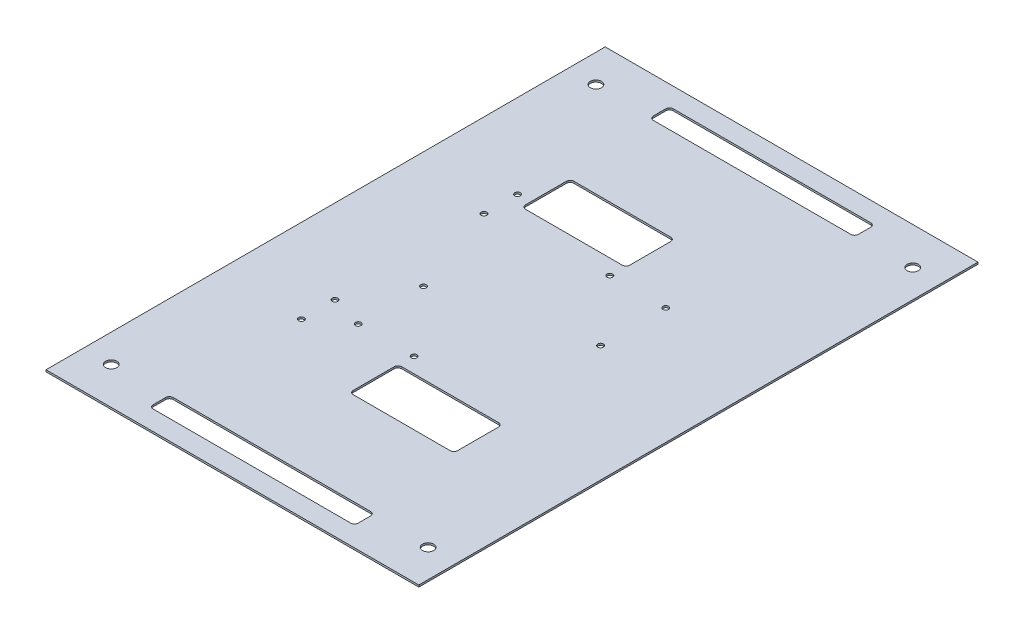
SolidWorks part; units mm, degrees
ref_plane "Plan de face" through (0, 0, 0) normal (0, 0, 1) x (1, 0, 0)
ref_plane "Plan de dessus" through (0, 0, 0) normal (0, 1, 0) x (1, 0, 0)
ref_plane "Plan de droite" through (0, 0, 0) normal (1, 0, 0) x (0, 0, -1)
sketch "Esquisse1" plane through (0, 0, 0) normal (0, 1, 0) x (1, 0, 0)
  line L0 (-2, -76.175) -> (42, -76.175) construction
  line L1 (-100, -150) -> (100, -150)
  line L2 (-100, -150) -> (-100, 150)
  line L3 (-100, 150) -> (100, 150)
  line L4 (100, -150) -> (100, 150)
  line L5 (-100, -150) -> (100, 150) construction
  line L6 (-100, 150) -> (100, -150) construction
  line L7 (-6, -53.175) -> (46, -53.175)
  line L8 (-8, -55.175) -> (-8, -77.175)
  line L9 (-6, -79.175) -> (46, -79.175)
  line L10 (48, -55.175) -> (48, -77.175)
  line L11 (47, -56.175) -> (-7, -56.175) construction
  line L12 (0, 0) -> (0, -150) construction
  line L13 (47, -150) -> (47, -53.175) construction
  line L14 (100, 0) -> (-100, 0) construction
  line L15 (-7, -53.175) -> (-7, -150) construction
  line L16 (0, 150) -> (0, 0) construction
  line L17 (7, 76.175) -> (-47, 76.175) construction
  line L18 (-46, 79.175) -> (6, 79.175)
  line L19 (-48, 77.175) -> (-48, 55.175)
  line L20 (-46, 53.175) -> (6, 53.175)
  line L21 (8, 77.175) -> (8, 55.175)
  line L22 (-47, 56.175) -> (7, 56.175) construction
  line L23 (-47, 56.175) -> (-47, 150) construction
  line L24 (-55, 0) -> (-55, 75.3308) construction
  line L25 (7, 56.175) -> (7, 150) construction
  line L26 (-53, -139.5001) -> (53, -139.5001)
  line L27 (55, -137.5001) -> (55, -130.7728)
  line L28 (53, -128.7728) -> (-53, -128.7728)
  line L29 (-60, -138.5001) -> (60, -138.5001) construction
  line L30 (57.5, -129.5001) -> (-57.5, -129.5001) construction
  line L31 (-55, -137.5001) -> (-55, -130.7728)
  line L32 (-55, 137.5001) -> (-55, 130.7728)
  line L33 (53, 128.7728) -> (-53, 128.7728)
  line L34 (55, 137.5001) -> (55, 130.7728)
  line L35 (-53, 139.5001) -> (53, 139.5001)
  arc A0 (46, -79.175) -> (48, -77.175) centre (46, -77.175) ccw
  arc A1 (48, -55.175) -> (46, -53.175) centre (46, -55.175) ccw
  arc A2 (-6, -53.175) -> (-8, -55.175) centre (-6, -55.175) ccw
  arc A3 (-8, -77.175) -> (-6, -79.175) centre (-6, -77.175) ccw
  arc A4 (8, 55.175) -> (6, 53.175) centre (6, 55.175) cw
  arc A5 (8, 77.175) -> (6, 79.175) centre (6, 77.175) ccw
  arc A6 (-46, 79.175) -> (-48, 77.175) centre (-46, 77.175) ccw
  arc A7 (-48, 55.175) -> (-46, 53.175) centre (-46, 55.175) ccw
  circle A8 centre (-37.5, -45) radius 1.5
  circle A9 centre (-7.5, -45) radius 1.5
  circle A10 centre (-37.5, -10) radius 1.5
  circle A11 centre (37.5, 10) radius 1.5
  circle A12 centre (37.5, 45) radius 1.5
  circle A13 centre (7.5, 45) radius 1.5
  circle A14 centre (85, 130) radius 3
  circle A15 centre (-85, 130) radius 3
  circle A16 centre (85, -130) radius 3
  circle A17 centre (-85, -130) radius 3
  circle A18 centre (-55, 40) radius 1.5
  circle A19 centre (-55, 58) radius 1.5
  circle A20 centre (-55, -58) radius 1.5
  circle A21 centre (-55, -40) radius 1.5
  arc A22 (53, -128.7728) -> (55, -130.7728) centre (53, -130.7728) cw
  arc A23 (53, -139.5001) -> (55, -137.5001) centre (53, -137.5001) ccw
  arc A24 (-55, -137.5001) -> (-53, -139.5001) centre (-53, -137.5001) ccw
  arc A25 (-55, -130.7728) -> (-53, -128.7728) centre (-53, -130.7728) cw
  arc A26 (-55, 130.7728) -> (-53, 128.7728) centre (-53, 130.7728) ccw
  arc A27 (-55, 137.5001) -> (-53, 139.5001) centre (-53, 137.5001) cw
  arc A28 (53, 128.7728) -> (55, 130.7728) centre (53, 130.7728) ccw
  arc A29 (53, 139.5001) -> (55, 137.5001) centre (53, 137.5001) cw
  point P0 (0, 0)
  point P93 (0, -139.5001)
  point P101 (0, -128.7728)
  point P107 (55, -128.7728)
  point P110 (55, -139.5001)
  point P113 (-55, -139.5001)
  point P116 (-55, -128.7728)
  point P119 (-55, 128.7728)
  point P122 (-55, 139.5001)
  point P125 (55, 128.7728)
  point P128 (55, 139.5001)
  dimension "D11" = 2
  dimension "D12" = 3
  dimension "D13" = 3
  dimension "D14" = 3
  dimension "D15" = 3
  dimension "D16" = 3
  dimension "D17" = 3
  dimension "D18" = 6
  dimension "D20" = 130
  dimension "D19" = 85
  dimension "D22" = 40
  dimension "D23" = 3
  dimension "D24" = 3
  dimension "D25" = 18
  dimension "D29" = 2
  dimension "D1" = 200
  dimension "D2" = 300
  dimension "D3" = 3
  dimension "D4" = 3
  dimension "D5" = 1
  dimension "D6" = 1
  dimension "D7" = 3
  dimension "D8" = 3
  dimension "D9" = 1
  dimension "D10" = 1
  dimension "D21" = 55
  dimension "D26" = 1
  dimension "D27" = 0.7272
  dimension "D28" = 55
extrude "Boss.-Extru.1" add sketch "Esquisse1" along normal blind 1
